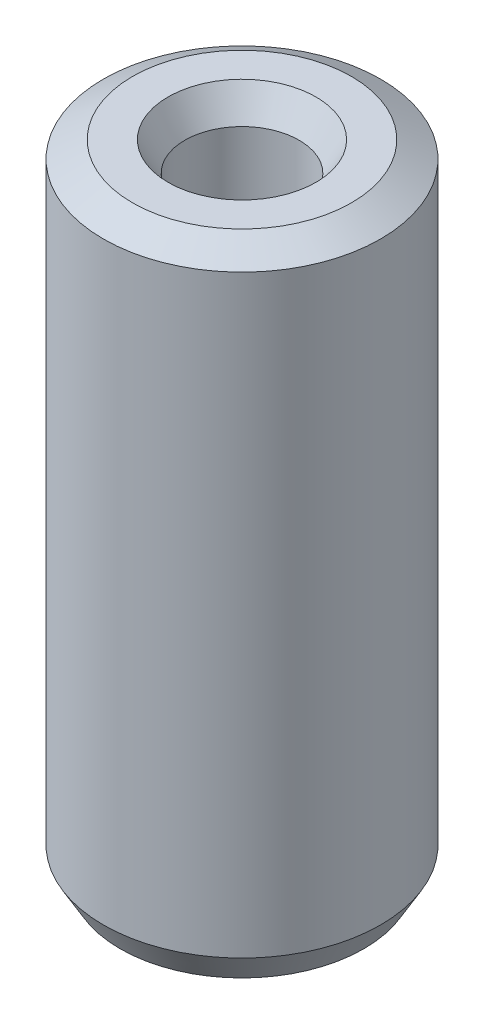
SolidWorks part; units mm, degrees
ref_plane "Front Plane" through (0, 0, 0) normal (0, 0, 1) x (1, 0, 0)
ref_plane "Top Plane" through (0, 0, 0) normal (0, 1, 0) x (1, 0, 0)
ref_plane "Right Plane" through (0, 0, 0) normal (1, 0, 0) x (0, 0, -1)
sketch "Sketch1" plane through (0, 0, 0) normal (0, 1, 0) x (1, 0, 0)
  circle A0 centre (0, 0) radius 22.5
  dimension "SLEEVE_OD" = 45
extrude "Boss-Extrude1" add sketch "Sketch1" along normal blind 103.9084
sketch "Sketch2" plane through (0, 0, 0) normal (0, 1, 0) x (1, 0, 0)
  circle A0 centre (0, 0) radius 9.2866
  dimension "BORE_D" = 18.5731
extrude "Cut-Extrude1" cut sketch "Sketch2" along normal through all
chamfer "Chamfer1" distance 2.727 angle 60 4 edges at (0, 103.9084, 9.2866) (0, 0, 9.2866) (0, 0, 22.5) (0, 103.9084, 22.5) first distance on face at (0, 103.9084, 9.2866) first distance on face at (0, 0, 9.2866) first distance on face at (0, 103.9084, 22.5)
